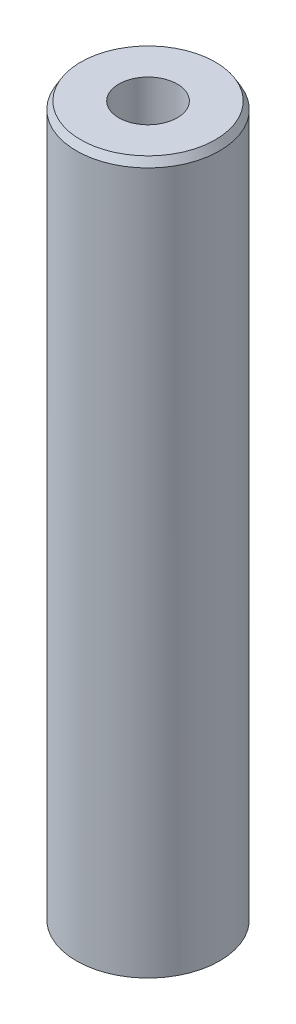
SolidWorks part; units mm, degrees
ref_plane "Front Plane" through (0, 0, 0) normal (0, 0, 1) x (1, 0, 0)
ref_plane "Top Plane" through (0, 0, 0) normal (0, 1, 0) x (1, 0, 0)
ref_plane "Right Plane" through (0, 0, 0) normal (1, 0, 0) x (0, 0, -1)
sketch "Sketch1" plane through (0, 0, 0) normal (0, 1, 0) x (1, 0, 0)
  circle A0 centre (0, 0) radius 47.5
  dimension "SHAFT_OD" = 95
extrude "Boss-Extrude1" add sketch "Sketch1" along normal blind 473.0164
sketch "Sketch2" plane through (0, 0, 0) normal (0, 1, 0) x (1, 0, 0)
  circle A0 centre (0, 0) radius 19.404
  dimension "BORE_D" = 38.808
extrude "Cut-Extrude1" cut sketch "Sketch2" along normal through all
chamfer "Chamfer1" distance 4.935 angle 30 2 edges at (0, 473.0164, 47.5) (0, 0, 47.5) first distance on face at (0, 473.0164, 47.5) first distance on face at (0, 0, 19.404)
